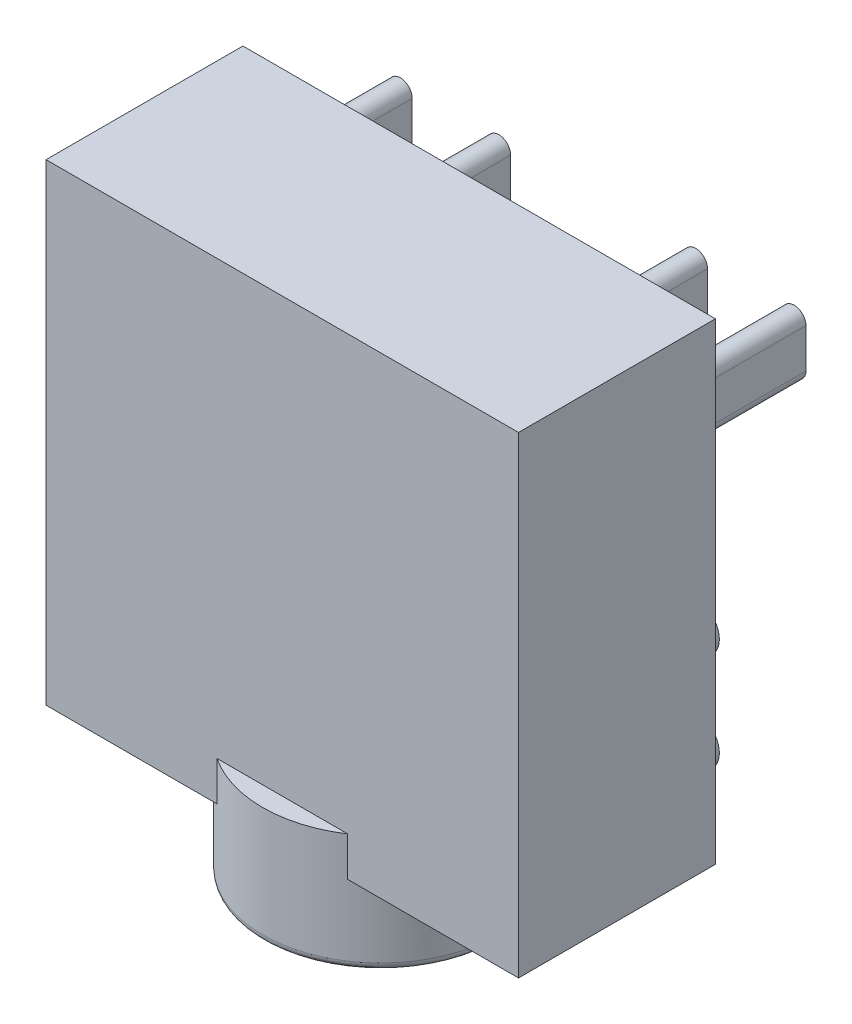
SolidWorks part; units mm, degrees
ref_plane "Front Plane" through (0, 0, 0) normal (0, 0, 1) x (1, 0, 0)
ref_plane "Top Plane" through (0, 0, 0) normal (0, 1, 0) x (1, 0, 0)
ref_plane "Right Plane" through (0, 0, 0) normal (1, 0, 0) x (0, 0, -1)
sketch "Sketch1" plane through (0, 0, 0) normal (0, 0, 1) x (1, 0, 0)
  line L1 (-6, -6) -> (6, -6)
  line L2 (-6, -6) -> (-6, 6)
  line L3 (-6, 6) -> (6, 6)
  line L4 (6, -6) -> (6, 6)
  line L5 (-6, -6) -> (6, 6) construction
  line L6 (-6, 6) -> (6, -6) construction
  point P0 (0, 0)
extrude "Boss-Extrude1" add sketch "Sketch1" along normal blind 5
sketch "Sketch2" plane through (0, -6, 0) normal (0, -1, 0) x (1, 0, 0)
  line L0 (-6, 5) -> (6, 0) construction
  line L1 (6, 5) -> (-6, 0) construction
  circle A0 centre (0, 2.5) radius 3
  circle A1 centre (0, 2.5) radius 1.8
extrude "Boss-Extrude2" add sketch "Sketch2" along normal blind 2 and the other way blind 1
fillet "Fillet1" radius 0.2 2 edges at (0, -8, 0.7) (0, -8, -0.5)
sketch "Sketch3" plane through (0, 0, 0) normal (0, 0, -1) x (-1, 0, 0)
  line L0 (-1.6583, -6) -> (-6, -6) construction
  line L1 (6, -6) -> (1.6583, -6) construction
  line L2 (-6, -6) -> (-6, 6) construction
  line L3 (6, 6) -> (6, -6) construction
  line L4 (0, -5) -> (0, 6) construction
  line L5 (1.6583, -5) -> (-1.6583, -5) construction
  line L6 (-6, 6) -> (6, 6) construction
  line L7 (-0.5, -1.5) -> (0.5, -1.5) construction
  line L8 (-0.5, -1.2) -> (0.5, -1.2)
  line L9 (-0.5, -1.8) -> (0.5, -1.8)
  line L10 (-6, 3.5) -> (6, 3.5) construction
  line L11 (-5, 4) -> (-5, 3) construction
  line L12 (-4.7, 4) -> (-4.7, 3)
  line L13 (-5.3, 4) -> (-5.3, 3)
  line L14 (-2.5, 4) -> (-2.5, 3) construction
  line L15 (-2.2, 4) -> (-2.2, 3)
  line L16 (-2.8, 4) -> (-2.8, 3)
  line L17 (5, 4) -> (5, 3) construction
  line L18 (4.7, 4) -> (4.7, 3)
  line L19 (5.3, 4) -> (5.3, 3)
  line L20 (2.5, 4) -> (2.5, 3) construction
  line L21 (2.2, 4) -> (2.2, 3)
  line L22 (2.8, 4) -> (2.8, 3)
  circle A0 centre (-5, -4) radius 0.6
  circle A1 centre (5, -4) radius 0.6
  circle A2 centre (-5, -1.5) radius 0.6
  circle A3 centre (5, -1.5) radius 0.6
  arc A4 (-0.5, -1.2) -> (-0.5, -1.8) centre (-0.5, -1.5) ccw
  arc A5 (0.5, -1.8) -> (0.5, -1.2) centre (0.5, -1.5) ccw
  arc A6 (-4.7, 4) -> (-5.3, 4) centre (-5, 4) ccw
  arc A7 (-5.3, 3) -> (-4.7, 3) centre (-5, 3) ccw
  arc A8 (-2.2, 4) -> (-2.8, 4) centre (-2.5, 4) ccw
  arc A9 (-2.8, 3) -> (-2.2, 3) centre (-2.5, 3) ccw
  arc A10 (4.7, 4) -> (5.3, 4) centre (5, 4) cw
  arc A11 (5.3, 3) -> (4.7, 3) centre (5, 3) cw
  arc A12 (2.2, 4) -> (2.8, 4) centre (2.5, 4) cw
  arc A13 (2.8, 3) -> (2.2, 3) centre (2.5, 3) cw
  circle A14 centre (0, 3.5) radius 0.6
  point P24 (0, -1.5)
  point P33 (-5, 3.5)
  point P41 (-2.5, 3.5)
  point P47 (5, 3.5)
  point P54 (2.5, 3.5)
  dimension "D1" = 2
  dimension "D5" = 2.5
  dimension "D7" = 1
  dimension "D10" = 2
  dimension "D2" = 2
  dimension "D3" = 1
  dimension "D4" = 1
  dimension "D6" = 2.5
  dimension "D8" = 0.6
  dimension "D9" = 5
extrude "Boss-Extrude3" add sketch "Sketch3" along normal blind 0.5 contours A0 | A3 | A1 | A14 | A2 region at (5, -4, 0) region at (-5, -4, 0) region at (-5, -1.5, 0)
extrude "Boss-Extrude4" add sketch "Sketch3<3>" along normal blind 3 contours A7 L12 A6 L13 | A9 L15 A8 L16 | A13 L21 A12 L22 | A11 L18 A10 L19 | L9 A5 L8 A4
sketch "Sketch3<3>" plane through (0, 0, 0) normal (0, 0, -1) x (-1, 0, 0) same geometry as "Sketch3"
